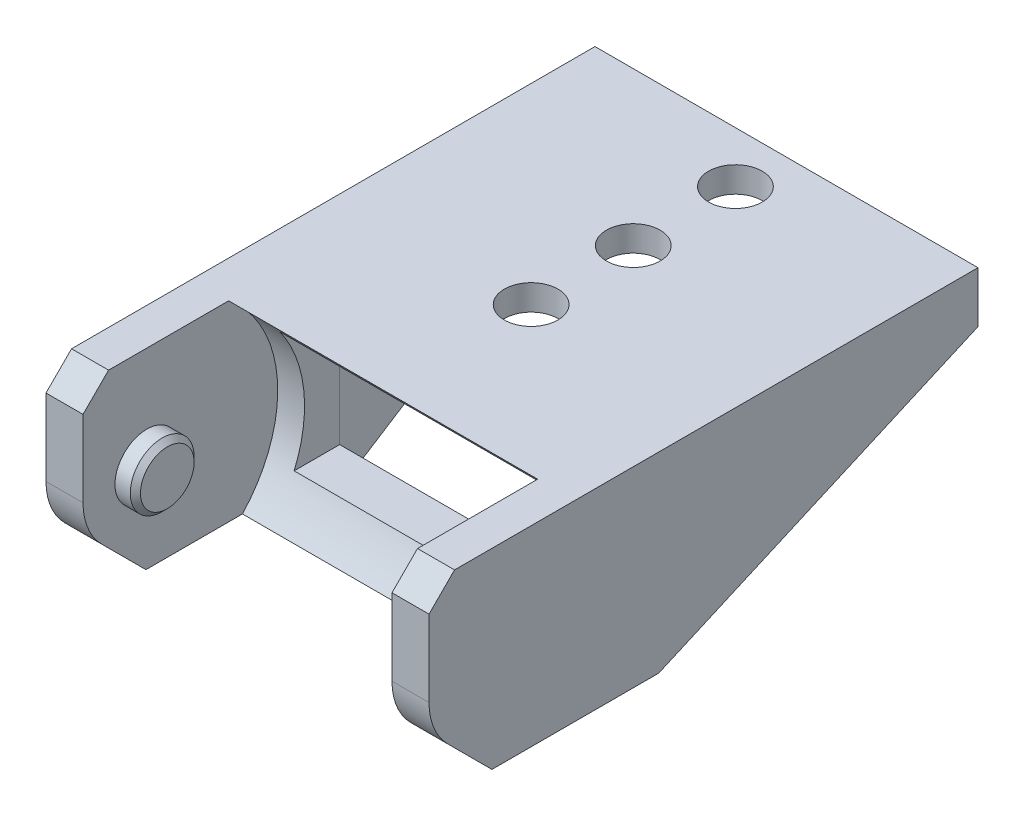
SolidWorks part; units mm, degrees
ref_plane "前基準面" through (0, 0, 0) normal (0, 0, 1) x (1, 0, 0)
ref_plane "上基準面" through (0, 0, 0) normal (0, 1, 0) x (1, 0, 0)
ref_plane "右基準面" through (0, 0, 0) normal (1, 0, 0) x (0, 0, -1)
sketch "草圖1" plane through (0, 0, 0) normal (0, 0, 1) x (1, 0, 0)
  line L1 (-12.751, 5.0503) -> (17.249, 5.0503)
  line L2 (-12.751, 5.0503) -> (-12.751, -9.9497)
  line L3 (-12.751, -9.9497) -> (17.249, -9.9497)
  line L4 (17.249, 5.0503) -> (17.249, -9.9497)
  dimension "D1" = 30
  dimension "D2" = 15
extrude "填料-伸長1" add sketch "草圖1" along normal blind 18
sketch "草圖2" plane through (0, 0, 18) normal (0, 0, 1) x (1, 0, 0)
  line L0 (-12.751, 5.0503) -> (-12.751, -9.9497) construction
  line L1 (-7.751, 3.0503) -> (12.249, 3.0503)
  line L2 (-7.751, 3.0503) -> (-7.751, -6.9497)
  line L3 (-7.751, -6.9497) -> (12.249, -6.9497)
  line L4 (12.249, 3.0503) -> (12.249, -6.9497)
  line L5 (17.249, -9.9497) -> (17.249, 5.0503) construction
  line L6 (17.249, 5.0503) -> (-12.751, 5.0503) construction
  line L7 (-12.751, -9.9497) -> (17.249, -9.9497) construction
  dimension "D1" = 5
  dimension "D2" = 5
  dimension "D3" = 2
  dimension "D4" = 3
extrude "除料-伸長1" cut sketch "草圖2" against normal up to next
sketch "草圖3" plane through (0, -6.9497, 0) normal (0, 1, 0) x (1, 0, 0)
  line L0 (-7.751, 0) -> (-7.751, -18) construction
  line L1 (-7.751, -6) -> (12.249, -6)
  line L2 (-7.751, -6) -> (-7.751, -18)
  line L3 (-7.751, -18) -> (12.249, -18)
  line L4 (12.249, -6) -> (12.249, -18)
  dimension "D1" = 12
extrude "除料-伸長2" cut sketch "草圖3" against normal up to next
sketch "草圖4" plane through (-7.751, 0, 0) normal (1, 0, 0) x (0, 0, -1)
  line L0 (-18, 3.0503) -> (-18, -9.9497) construction
  line L1 (-18, -9.9497) -> (-6, -9.9497) construction
  line L3 (-13, -2.9497) -> (-18, -2.9497)
  line L4 (-13, -2.9497) -> (-13, 7.8945)
  line L5 (-18, -2.9497) -> (-18, 7.8945)
  line L6 (-13, 7.8945) -> (-18, 7.8945)
  circle A0 centre (-13, -2.9497) radius 10.25
  line M3 (0, 3.0503) -> (-18, 3.0503)
  line M4 (-18, 3.0503) -> (-18, -9.9497)
  line M5 (-18, -9.9497) -> (-6, -9.9497)
  line M6 (-6, -9.9497) -> (-6, -6.9497)
  line M7 (-6, -6.9497) -> (0, -6.9497)
  dimension "D2" = 7
  dimension "D3" = 20.5
  dimension "D1" = 5
extrude "除料-伸長5" cut sketch "草圖4" against normal blind 2.1 and the other way blind 22.1 contours L3 L4 M3 M4 | A0 L4 L3 M7 M3 M4 M5 M6 | A0 L4 L6 L5 | A0 L4 M3 | L4 A0 L5 M3 | L5 A0 M7 M6 M5 M4 region at (-7.751, -3.92, 9.9772) region at (-7.751, 0.0503, 15.5) region at (-7.751, -6.4497, 18.275) region at (-7.751, 4.9834, 15.3602) region at (-7.751, 4.7846, 9.7748) region at (-7.751, 7.3136, 16.0262)
sketch "草圖5" plane through (14.349, 0, 0) normal (-1, 0, 0) x (0, 0, 1)
  circle A0 centre (13, -2.9497) radius 2.5
  arc A2 (6.592, 5.0503) -> (5.5125, -9.9497) centre (13, -2.9497) ccw construction
  dimension "D1" = 5
extrude "填料-伸長2" add sketch "草圖5" along normal blind 1.6
sketch "草圖6" plane through (-9.851, 0, 0) normal (1, 0, 0) x (0, 0, -1)
  circle A0 centre (-13, -2.9497) radius 2.5
  arc A1 (-5.5125, -9.9497) -> (-6.592, 5.0503) centre (-13, -2.9497) ccw construction
  dimension "D1" = 5
extrude "填料-伸長3" add sketch "草圖6" along normal blind 1.6
chamfer "導角1" distance 0.4 angle 45 2 edges at (-8.251, -0.4497, 13) (12.749, -5.4497, 13)
sketch "草圖7" plane through (-9.851, 0, 0) normal (1, 0, 0) x (0, 0, -1)
  line L0 (-13.0711, -9.9497) -> (-18, -5.0208)
  line L1 (-18, -9.9497) -> (-5.5125, -9.9497) construction
  line L2 (-18, -9.9497) -> (-18, 5.0503) construction
  circle A0 centre (-13, -2.9497) radius 2.5 construction
  line M4 (-18, 5.0503) -> (-18, -9.9497)
  line M5 (-18, -9.9497) -> (-5.5125, -9.9497)
  dimension "D1" = 45
  dimension "D2" = 5
extrude "除料-伸長6" cut sketch "草圖7" against normal through all both and the other way through all contours L0 M5 M4 region at (-9.851, -8.3067, 16.357)
sketch "草圖8" plane through (-9.851, 0, 0) normal (1, 0, 0) x (0, 0, -1)
  line L0 (-18, -5.0208) -> (-18, -2.9497)
  line L1 (-18, -5.0208) -> (-15.5355, -7.4853)
  line L2 (-13.0711, -9.9497) -> (-18, -5.0208) construction
  circle A0 centre (-13, -2.9497) radius 5
  line M1 (-18, -5.0208) -> (-13.0711, -9.9497)
  line M5 (-18, 5.0503) -> (-18, -5.0208)
extrude "除料-伸長7" cut sketch "草圖8" against normal through all both and the other way through all contours A0 M5 M1 region at (-9.851, -4.8962, 17.6992)
chamfer "導角2" distance 2 angle 45 2 edges at (15.799, 5.0503, 18) (-11.301, 5.0503, 18)
sketch "草圖9" plane through (0, 0, 0) normal (0, 0, -1) x (-1, 0, 0)
  line L0 (-12.249, 3.0503) -> (-12.249, -9.9497)
  line L1 (12.751, -9.9497) -> (-17.249, -9.9497) construction
  line L2 (-12.249, -9.9497) -> (-17.249, -9.9497)
  line L3 (-17.249, -9.9497) -> (-17.249, 5.0503)
  line L4 (-17.249, 5.0503) -> (12.751, 5.0503)
  line L5 (12.751, 5.0503) -> (12.751, -9.9497)
  line L6 (7.751, 3.0503) -> (7.751, -9.9497)
  line L7 (7.751, -9.9497) -> (12.751, -9.9497)
  line L8 (-12.249, 3.0503) -> (7.751, 3.0503)
extrude "填料-伸長4" add sketch "草圖9" along normal blind 25
chamfer "導角3" distance 25 distance2 11 2 edges at (-10.251, -9.9497, -25) (14.749, -9.9497, -25) first distance on face at (2.249, -9.9497, -3.0576)
sketch "草圖10" plane through (0, 3.0503, 0) normal (0, -1, 0) x (1, 0, 0)
  line L0 (12.249, -25) -> (12.249, 4.6896) construction
  line L1 (12.249, -25) -> (-7.751, -25) construction
  circle A0 centre (2.249, -21) radius 2.1
  circle A1 centre (2.249, -13) radius 2.1
  circle A2 centre (2.249, -5) radius 2.1
  dimension "D1" = 10
  dimension "D2" = 4
  dimension "D3" = 4.2
  dimension "D4" = 3
extrude "除料-伸長8" cut sketch "草圖10" against normal blind 15
chamfer "導角4" distance 25 distance2 3 2 edges at (-7.751, 2.0503, -25) (12.249, 2.0503, -25) first distance on face at (-7.751, -2.7584, -7.1766) first distance on face at (12.249, -2.7584, -7.1766)
